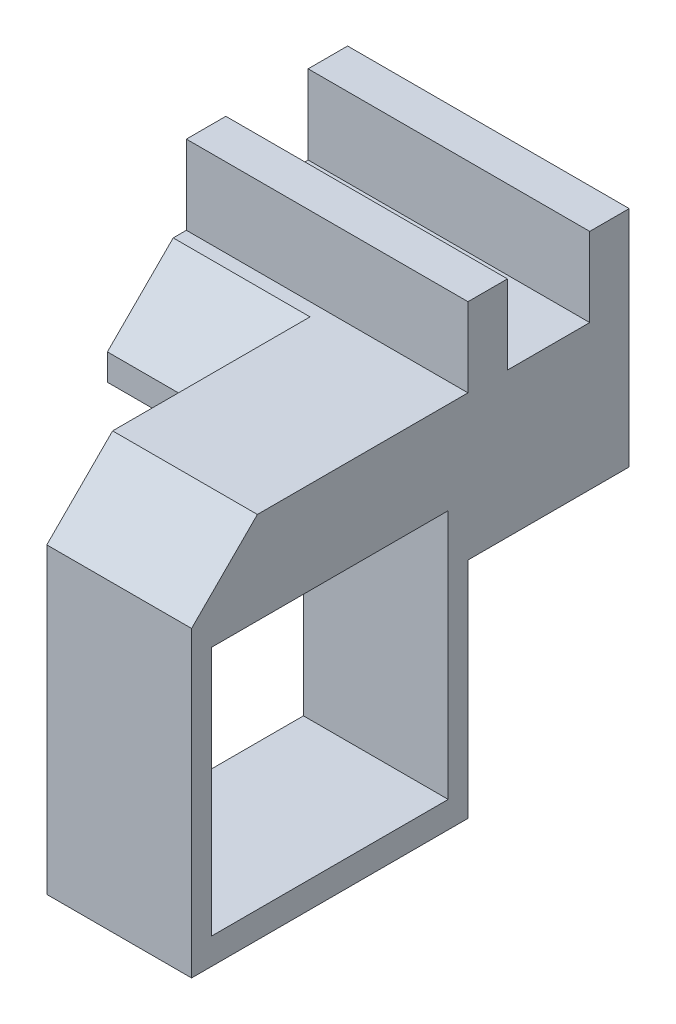
SolidWorks part; units mm, degrees
note: '?' marks a value the reader was unsure of. The reader was unsure of these and kept them because the rebuilt part matched: shared geometry of "Sketch1<3>", "Sketch1<6>".
ref_plane "Vehicle Ground Plane" through (0, 0, 0) normal (0, 0, 1) x (1, 0, 0)
ref_plane "Vehicle Centreline Plane" through (0, 0, 0) normal (0, 1, 0) x (1, 0, 0)
ref_plane "Front Roll Hoop Plane" through (0, 0, 0) normal (1, 0, 0) x (0, 0, -1)
ref_axis "X-Axis" through (-88.99, 0, 0) along (1, 0, 0)?
ref_axis "Y-Axis" through (0, 55, 0) along (0, -1, 0)?
ref_axis "Z-Axis" through (0, 0, -88.99) along (0, 0, 1)?
sketch "Sketch1" plane through (0, 0, 0) normal (0, 1, 0) x (1, 0, 0)
  line L0 (0.9451, 0) -> (0.9451, -12.5)
  line L5 (1.8901, 0) -> (0, 0)
  line L6 (0.9451, -12.5) -> (21.735, -12.5)
  line L7 (0.9451, -12.5) -> (0.9451, -18.5)
  line L8 (32.735, -18.5) -> (32.735, -60.5)
  line L9 (0.9451, -18.5) -> (0.9451, -30.5)
  line L10 (0.9451, 0) -> (21.735, 0)
  line L11 (-55, 0) -> (55, 0) construction
  line L12 (21.735, 0) -> (21.735, -18.5)
  line L13 (21.735, -18.5) -> (0.9451, -18.5)
  line L14 (0.9451, 0) -> (0.9451, 6)
  line L15 (0.9451, 6) -> (21.735, 6)
  line L16 (21.735, 6) -> (21.735, 0)
  line L17 (0.9451, -18.5) -> (21.735, -18.5)
  line L18 (0.9451, -30.5) -> (21.735, -30.5)
  line L19 (21.735, -30.5) -> (21.735, -18.5)
  line L20 (21.735, -18.5) -> (21.735, 6)
  line L21 (0.9451, 6) -> (0.9451, -18.5)
  line L22 (21.735, -30.5) -> (21.735, -60.5)
  line L23 (21.735, -60.5) -> (43.735, -60.5)
  line L24 (43.735, -60.5) -> (43.735, -30.5)
  line L25 (43.735, -30.5) -> (43.735, -18.5)
  line L26 (21.735, -18.5) -> (43.735, -18.5)
  line L27 (43.735, -30.5) -> (43.735, -18.5)
  line L28 (43.735, 0) -> (43.735, -18.5)
  line L29 (64.525, -12.5) -> (43.735, -12.5)
  line L30 (43.735, -18.5) -> (64.525, -18.5)
  line L31 (64.525, -30.5) -> (43.735, -30.5)
  line L32 (64.525, 6) -> (43.735, 6)
  line L33 (43.735, 6) -> (43.735, 0)
  line L34 (64.525, 6) -> (64.525, -18.5)
  line L35 (64.525, 0) -> (64.525, 6)
  line L36 (64.525, -18.5) -> (64.525, -30.5)
  line L37 (64.525, -12.5) -> (64.525, -18.5)
  line L38 (64.525, 0) -> (64.525, -12.5)
  line L39 (43.735, 0) -> (64.525, 0)
  point P6 (0.9451, 0)
  point P31 (64.525, 0)
  dimension "D1" = 12.5
  dimension "D2" = 6
  dimension "D3" = 12
  dimension "D4" = 6
  dimension "D5" = 30
  dimension "D6" = 22
  dimension "D7" = 20.79
  dimension "D8" = 0.9451
extrude "Boss-Extrude2" add sketch "Sketch1" along normal blind 23 contours L16 L15 L14 L5 L10 | L13 L12 L6 L7 | L34 L29 L28 L30 | L33 L39 L34 L32
extrude "Boss-Extrude3" add sketch "Sketch1<3>" against normal blind 11 contours L13 L12 L6 L7 | L12 L10 L5 L0 L6 | L16 L15 L14 L5 L10 | L39 L28 L29 L34 | L36 L30 L25 L31 | L34 L29 L28 L30 | L33 L39 L34 L32
sketch "Sketch1<3>" plane through (0, 0, 0) normal (0, 1, 0) x (1, 0, 0) same geometry as "Sketch1"
extrude "Boss-Extrude5" add sketch "Sketch1<6>" against normal blind 45 contours L26 L8 L23 L24 L25 | L26 L19 L22 L23 L8
sketch "Sketch1<6>" plane through (0, 0, 0) normal (0, 1, 0) x (1, 0, 0) same geometry as "Sketch1"
ref_plane "Plane1" through (74.525, 0, 0) normal (1, 0, 0) x (0, 0, -1)
sketch "Sketch2" plane through (74.525, 0, 0) normal (1, 0, 0) x (0, 0, -1)
  line L0 (6, 0) -> (-30.5, 0) construction
  line L1 (-30.5, 0) -> (-30.5, -11) construction
  line L2 (-30.5, -11) -> (6, -11) construction
  line L3 (6, -11) -> (6, 0) construction
  line L4 (-18.5, -45) -> (-18.5, -11) construction
  line L5 (-18.5, -11) -> (-30.5, -11) construction
  line L6 (-30.5, -11) -> (-30.5, 0) construction
  line L7 (-30.5, 0) -> (-60.5, 0) construction
  line L8 (-60.5, 0) -> (-60.5, -45) construction
  line L9 (-60.5, -45) -> (-18.5, -45) construction
  line L10 (6, 0) -> (-30.5, 0)
  line L11 (-30.5, 0) -> (-30.5, -11)
  line L12 (-30.5, -11) -> (6, -11)
  line L13 (6, -11) -> (6, 0)
  line L14 (-18.5, -45) -> (-18.5, -11)
  line L15 (-18.5, -11) -> (-30.5, -11)
  line L16 (-30.5, -11) -> (-30.5, 0)
  line L17 (-30.5, 0) -> (-60.5, 0)
  line L18 (-60.5, 0) -> (-60.5, -45)
  line L19 (-60.5, -45) -> (-18.5, -45)
  line L20 (-60.5, -14.9897) -> (-57.5, -14.9897)
  line L21 (-34.5516, -45) -> (-34.5516, -42)
  line L22 (-41.1839, 0) -> (-41.1839, -3)
  line L23 (-57.5, -41) -> (-21.5, -41)
  line L24 (-57.5, -41) -> (-57.5, -3)
  line L25 (-57.5, -3) -> (-21.5, -3)
  line L26 (-21.5, -41) -> (-21.5, -3)
  dimension "D1" = 3
  dimension "D2" = 3
  dimension "D3" = 3
  dimension "D4" = 3
  dimension "D5" = 38
  dimension "D6" = 36
extrude "Cut-Extrude1" cut sketch "Sketch2" against normal through all contours L23 L26 L12 L16 L25 L24 | L12 L26 L25 L16
sketch "Sketch3" plane through (43.735, 0, 0) normal (-1, 0, 0) x (0, 0, 1)
  line L1 (-6, 0) -> (18.5, 0)
  line L2 (-6, 0) -> (-6, -11)
  line L3 (-6, -11) -> (18.5, -11)
  line L4 (18.5, 0) -> (18.5, -11)
extrude "Boss-Extrude6" add sketch "Sketch3" along normal blind 42
sketch "Sketch4" plane through (0, 0, 0) normal (0, 1, 0) x (1, 0, 0)
  line L0 (0.9451, -18.5) -> (64.525, -18.5)
  line L20 (64.525, -18.5) -> (43.735, -18.5)
  line L21 (43.735, -18.5) -> (43.735, -12.5)
  line L22 (43.735, -12.5) -> (64.525, -12.5)
  line L23 (64.525, -12.5) -> (64.525, 0)
  line L24 (64.525, 0) -> (43.735, 0)
  line L25 (43.735, 0) -> (43.735, 6)
  line L26 (43.735, 6) -> (21.735, 6)
  line L27 (21.735, 6) -> (21.735, 0)
  line L28 (21.735, 0) -> (0.9451, 0)
  line L29 (0.9451, 0) -> (0.9451, -12.5)
  line L30 (0.9451, -12.5) -> (21.735, -12.5)
  line L31 (21.735, -12.5) -> (21.735, -18.5)
  line L32 (21.735, -18.5) -> (0.9451, -18.5)
  line L33 (0.9451, -18.5) -> (0.9451, -30.5)
  line L34 (0.9451, -30.5) -> (21.735, -30.5)
  line L35 (21.735, -30.5) -> (21.735, -60.5)
  line L36 (21.735, -60.5) -> (43.735, -60.5)
  line L37 (43.735, -60.5) -> (43.735, -30.5)
  line L38 (43.735, -30.5) -> (64.525, -30.5)
  line L39 (64.525, -30.5) -> (64.525, -18.5)
  line L40 (64.525, -18.5) -> (43.735, -18.5)
  line L41 (43.735, -18.5) -> (43.735, -12.5)
  line L42 (43.735, -12.5) -> (64.525, -12.5)
  line L43 (64.525, -12.5) -> (64.525, 0)
  line L44 (64.525, 0) -> (43.735, 0)
  line L45 (43.735, 0) -> (43.735, 6)
  line L46 (43.735, 6) -> (21.735, 6)
  line L47 (21.735, 6) -> (21.735, 0)
  line L48 (21.735, 0) -> (0.9451, 0)
  line L49 (0.9451, 0) -> (0.9451, -12.5)
  line L50 (0.9451, -12.5) -> (21.735, -12.5)
  line L51 (21.735, -12.5) -> (21.735, -18.5)
  line L52 (21.735, -18.5) -> (0.9451, -18.5)
  line L53 (0.9451, -18.5) -> (0.9451, -30.5)
  line L54 (0.9451, -30.5) -> (21.735, -30.5)
  line L55 (21.735, -30.5) -> (21.735, -60.5)
  line L56 (21.735, -60.5) -> (43.735, -60.5)
  line L57 (43.735, -60.5) -> (43.735, -30.5)
  line L58 (43.735, -30.5) -> (64.525, -30.5)
  line L59 (64.525, -30.5) -> (64.525, -18.5)
  dimension "D1" = 0
extrude "Boss-Extrude7" add sketch "Sketch4" along normal blind 11 contours L40 L41 L42 L43 L44 L45 L46 L47 L48 L49 L50 L51 L52 L53 L54 L55 L56 L57 L58 L59
chamfer "Chamfer2" distance 10 angle 45 3 edges at (32.735, 11, 60.5) (54.13, 11, 30.5) (11.3401, 11, 30.5)
sketch "Sketch5" plane through (0, 0, -6) normal (0, 0, -1) x (-1, 0, 0)
  line L0 (-0.9451, -11) -> (-64.525, -11) construction
  line L1 (-64.525, 23) -> (-43.735, 23)
  line L2 (-64.525, 23) -> (-64.525, -11)
  line L3 (-64.525, -11) -> (-43.735, -11)
  line L4 (-43.735, 23) -> (-43.735, -11)
  line L5 (-21.735, -11) -> (-43.735, -11) construction
extrude "Cut-Extrude2" cut sketch "Sketch5" against normal through all
sketch "Sketch6" plane through (21.735, 0, 0) normal (1, 0, 0) x (0, 0, -1)
  line L1 (-18.5, 23) -> (-12.5, 23)
  line L2 (-18.5, 23) -> (-18.5, 11)
  line L3 (-18.5, 11) -> (-12.5, 11)
  line L4 (-12.5, 23) -> (-12.5, 11)
  line L5 (0, 23) -> (6, 23)
  line L6 (0, 23) -> (0, 11)
  line L7 (0, 11) -> (6, 11)
  line L8 (6, 23) -> (6, 11)
extrude "Boss-Extrude8" add sketch "Sketch6" along normal blind 22
equation "\"x-bitch\"=12"
equation "\"D3@Sketch1\"=\"x-bitch\""
